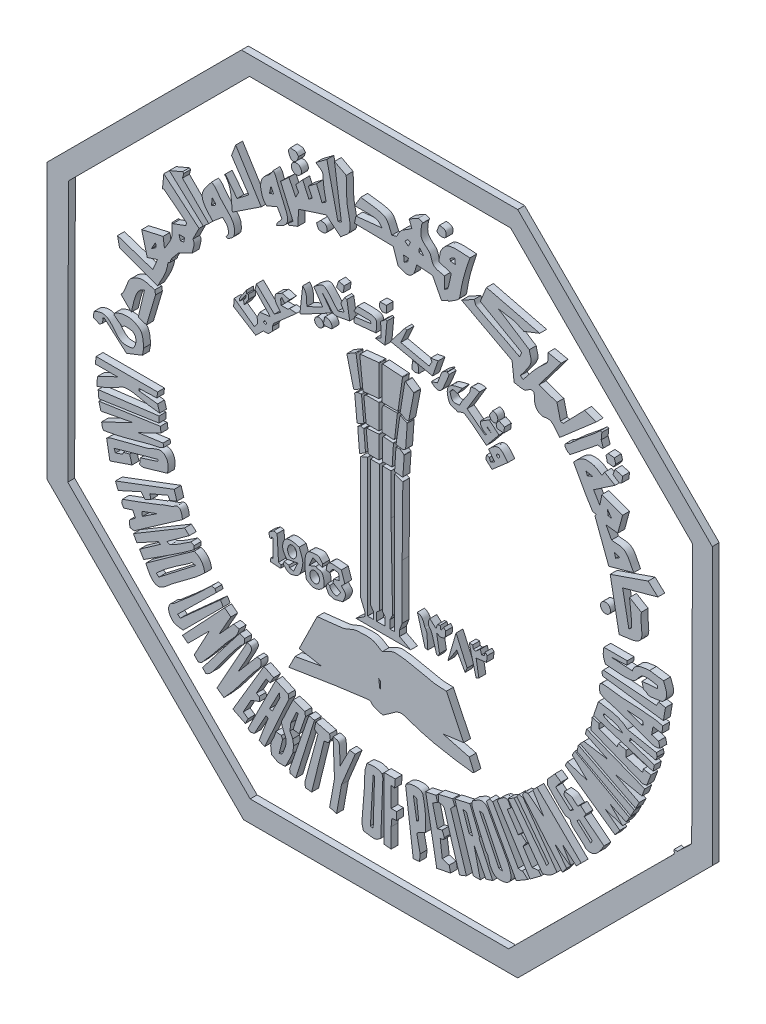
SolidWorks part; units mm, degrees
ref_plane "Front Plane" through (0, 0, 0) normal (0, 0, 1) x (1, 0, 0)
ref_plane "Top Plane" through (0, 0, 0) normal (0, 1, 0) x (1, 0, 0)
ref_plane "Right Plane" through (0, 0, 0) normal (1, 0, 0) x (0, 0, -1)
sketch "Sketch3" plane through (0, 0, 0) normal (0, 0, 1) x (1, 0, 0)
  line L0 (183.5, 512) -> (917.5, 512) construction
  line L1 (600.8403, 692.74) -> (593.4471, 654.6425)
  line L2 (592.7925, 654.1027) -> (589.1017, 654.1027)
  line L3 (588.7776, 654.1868) -> (581.4635, 658.2556)
  line L4 (581.1293, 658.9439) -> (587.8348, 700.7525)
  line L5 (588.8625, 701.202) -> (600.5551, 693.4222)
  line L6 (577.2635, 658.4827) -> (555.6388, 658.4827)
  line L7 (554.972, 659.1494) -> (554.972, 706.3571)
  line L8 (555.6867, 707.0222) -> (583.8131, 704.9983)
  line L9 (584.4252, 704.2383) -> (577.9235, 659.0545)
  line L10 (549.9929, 705.9322) -> (523.2286, 703.097)
  line L11 (522.6358, 702.3637) -> (527.2139, 659.1457)
  line L12 (527.9472, 658.5529) -> (550.1334, 660.9031)
  line L13 (550.7299, 661.5661) -> (550.7299, 705.2691)
  line L14 (516.2122, 701.2896) -> (504.2243, 694.3379)
  line L15 (503.9122, 693.5982) -> (513.7065, 654.7226)
  line L16 (514.6876, 654.3087) -> (523.3973, 659.3593)
  line L17 (523.7213, 660.0414) -> (517.2051, 700.818)
  line L18 (588.6228, 616.3203) -> (585.1923, 614.331)
  line L19 (584.7629, 614.2479) -> (575.7308, 615.5475)
  line L20 (575.1658, 616.3025) -> (580.6493, 654.4101)
  line L21 (581.5764, 654.926) -> (590.8926, 650.853)
  line L22 (591.2907, 650.1954) -> (588.9535, 616.8505)
  line L23 (554.972, 658.4827) -> (554.972, 651.522)
  line L24 (554.972, 651.3934) -> (554.972, 621.5863)
  line L25 (555.6388, 620.9195) -> (559.0252, 620.9195)
  line L26 (559.0252, 620.9195) -> (569.6504, 620.1748)
  line L27 (569.8466, 620.1901) -> (572.5562, 620.8139)
  line L28 (573.0691, 621.3872) -> (576.974, 655.2418)
  line L29 (576.3116, 655.985) -> (557.211, 655.985)
  line L30 (556.592, 655.5662) -> (555.0199, 651.6413)
  line L31 (550.7299, 655.3182) -> (550.7299, 620.8346)
  line L32 (550.0631, 620.1678) -> (532.4115, 620.1678)
  line L33 (531.7479, 620.77) -> (528.5662, 653.4609)
  line L34 (528.8679, 654.0855) -> (531.6413, 655.8782)
  line L35 (532.0032, 655.985) -> (550.0631, 655.985)
  line L36 (525.1693, 653.2014) -> (528.4808, 619.1764)
  line L37 (528.0939, 618.5052) -> (519.538, 614.6026)
  line L38 (518.5977, 615.1446) -> (515.1964, 650.0925)
  line L39 (515.4981, 650.7171) -> (519.3922, 653.2343)
  line L40 (519.6896, 653.338) -> (524.4411, 653.8004)
  line L41 (575.6634, 612.7708) -> (580.838, 612.7708)
  line L42 (581.2309, 612.6428) -> (586.6507, 608.6901)
  line L43 (586.9229, 608.1048) -> (584.9596, 580.0932)
  line L44 (584.218, 579.4774) -> (573.6441, 580.697)
  line L45 (573.055, 581.4015) -> (574.9979, 612.1461)
  line L46 (570.0808, 398.9926) -> (567.8514, 519.8754)
  line L47 (571.3406, 614.6961) -> (569.4688, 585.0752)
  line L48 (568.8033, 584.4505) -> (556.5327, 584.4505)
  line L49 (555.8659, 585.1173) -> (555.8659, 615.743)
  line L50 (556.58, 616.4081) -> (570.7224, 615.4032)
  line L51 (550.7299, 615.7346) -> (550.7299, 584.4371)
  line L52 (550.0631, 583.7703) -> (535.4407, 583.7703)
  line L53 (534.777, 584.3725) -> (531.872, 614.2211)
  line L54 (532.4807, 614.9501) -> (550.0082, 616.3991)
  line L55 (528.5686, 611.7562) -> (530.8774, 583.8285)
  line L56 (530.5749, 583.2136) -> (523.2513, 578.4794)
  line L57 (522.2248, 578.9845) -> (519.6423, 610.2237)
  line L58 (519.9448, 610.8386) -> (523.3827, 613.0609)
  line L59 (523.8705, 613.1558) -> (528.03, 612.3561)
  line L60 (584.9102, 573.7645) -> (584.002, 475.2058)
  line L61 (584.002, 475.2058) -> (584.002, 396.0105)
  line L62 (583.9958, 395.9763) -> (580.1051, 385.6875)
  line L63 (580.0989, 385.6534) -> (580.0989, 377.5979)
  line L64 (580.1498, 377.5128) -> (596.2129, 368.9076)
  line L66 (596.2129, 368.9076) -> (547.0228, 368.9076)
  line L67 (546.9262, 368.8111) -> (546.9262, 369.0041)
  line L68 (546.8297, 368.9076) -> (517.4836, 368.9076)
  line L69 (517.4301, 369.0845) -> (530.4913, 377.7813)
  line L70 (530.5343, 377.8617) -> (530.5343, 382.2535)
  line L71 (530.5269, 382.2908) -> (523.8569, 398.248)
  line L72 (523.8494, 398.2853) -> (523.8494, 574.8342)
  line L73 (523.9087, 574.9233) -> (533.6801, 579.0077)
  line L74 (533.8139, 578.9186) -> (533.8139, 380.138)
  line L75 (533.9104, 380.0414) -> (542.1654, 380.0414)
  line L76 (542.2619, 380.138) -> (542.2619, 390.2402)
  line L77 (542.2457, 390.2937) -> (538.0541, 396.5888)
  line L78 (538.0379, 396.6423) -> (538.0379, 578.967)
  line L79 (538.1344, 579.0636) -> (551.2096, 579.0636)
  line L80 (551.3061, 578.967) -> (551.3061, 476.3053)
  line L82 (551.3061, 476.3053) -> (551.3061, 395.4793)
  line L83 (551.271, 395.4048) -> (547.0491, 391.9257)
  line L84 (547.0139, 391.8512) -> (547.0139, 380.138)
  line L85 (547.1104, 380.0414) -> (559.1217, 380.0414)
  line L86 (559.2182, 380.138) -> (559.2182, 391.8621)
  line L87 (559.1962, 391.9235) -> (555.3537, 396.5864)
  line L88 (555.3317, 396.6478) -> (555.3317, 578.967)
  line L89 (555.4282, 579.0636) -> (567.7548, 579.0636)
  line L90 (567.8514, 578.967) -> (567.8514, 519.8754)
  line L93 (570.0694, 398.9479) -> (566.3034, 391.9181)
  line L94 (566.292, 391.8725) -> (566.292, 380.138)
  line L95 (566.3885, 380.0414) -> (572.9186, 380.0414)
  line L96 (573.0151, 380.138) -> (573.0151, 577.8627)
  line L97 (573.1435, 577.9538) -> (584.8456, 573.8565)
  arc A0 (523.2513, 578.4794) -> (522.2248, 578.9845) centre (522.8893, 579.0394) cw
  arc A1 (530.8774, 583.8285) -> (530.5749, 583.2136) centre (530.2129, 583.7735) cw
  arc A2 (519.6423, 610.2237) -> (519.9448, 610.8386) centre (520.3068, 610.2787) cw
  arc A3 (523.3827, 613.0609) -> (523.8705, 613.1558) centre (523.7446, 612.501) cw
  arc A4 (528.5686, 611.7562) -> (528.03, 612.3561) centre (527.9041, 611.7013) ccw
  arc A5 (531.872, 614.2211) -> (532.4807, 614.9501) centre (532.5357, 614.2856) cw
  arc A6 (550.7299, 615.7346) -> (550.0082, 616.3991) centre (550.0631, 615.7346) ccw
  arc A7 (535.4407, 583.7703) -> (534.777, 584.3725) centre (535.4407, 584.4371) cw
  arc A8 (550.7299, 584.4371) -> (550.0631, 583.7703) centre (550.0631, 584.4371) cw
  arc A9 (556.5327, 584.4505) -> (555.8659, 585.1173) centre (556.5327, 585.1173) cw
  arc A10 (569.4688, 585.0752) -> (568.8033, 584.4505) centre (568.8033, 585.1173) cw
  arc A11 (555.8659, 615.743) -> (556.58, 616.4081) centre (556.5327, 615.743) cw
  arc A12 (571.3406, 614.6961) -> (570.7224, 615.4032) centre (570.6752, 614.7381) ccw
  arc A13 (586.6507, 608.6901) -> (586.9229, 608.1048) centre (586.2578, 608.1514) cw
  arc A14 (580.838, 612.7708) -> (581.2309, 612.6428) centre (580.838, 612.1041) cw
  arc A15 (575.6634, 612.7708) -> (574.9979, 612.1461) centre (575.6634, 612.1041) ccw
  arc A16 (573.6441, 580.697) -> (573.055, 581.4015) centre (573.7205, 581.3594) cw
  arc A17 (584.9596, 580.0932) -> (584.218, 579.4774) centre (584.2944, 580.1398) cw
  arc A18 (515.1964, 650.0925) -> (515.4981, 650.7171) centre (515.86, 650.1571) cw
  arc A19 (519.3922, 653.2343) -> (519.6896, 653.338) centre (519.7542, 652.6744) cw
  arc A20 (525.1693, 653.2014) -> (524.4411, 653.8004) centre (524.5057, 653.1368) ccw
  arc A21 (519.538, 614.6026) -> (518.5977, 615.1446) centre (519.2613, 615.2092) cw
  arc A22 (528.4808, 619.1764) -> (528.0939, 618.5052) centre (527.8172, 619.1118) cw
  arc A23 (532.4115, 620.1678) -> (531.7479, 620.77) centre (532.4115, 620.8346) cw
  arc A24 (528.5662, 653.4609) -> (528.8679, 654.0855) centre (529.2299, 653.5255) cw
  arc A25 (531.6413, 655.8782) -> (532.0032, 655.985) centre (532.0032, 655.3182) cw
  arc A26 (550.7299, 655.3182) -> (550.0631, 655.985) centre (550.0631, 655.3182) ccw
  arc A27 (550.7299, 620.8346) -> (550.0631, 620.1678) centre (550.0631, 620.8346) cw
  arc A28 (554.972, 621.5863) -> (555.6388, 620.9195) centre (555.6388, 621.5863) ccw
  arc A29 (569.6504, 620.1748) -> (569.8466, 620.1901) centre (569.697, 620.8399) ccw
  arc A30 (572.5562, 620.8139) -> (573.0691, 621.3872) centre (572.4067, 621.4636) ccw
  arc A31 (555.0199, 651.6413) -> (554.972, 651.3934) centre (555.6388, 651.3934) ccw
  arc A32 (557.211, 655.985) -> (556.592, 655.5662) centre (557.211, 655.3182) ccw
  arc A33 (576.974, 655.2418) -> (576.3116, 655.985) centre (576.3116, 655.3182) ccw
  arc A34 (588.6228, 616.3203) -> (588.9535, 616.8505) centre (588.2883, 616.8972) ccw
  arc A35 (585.1923, 614.331) -> (584.7629, 614.2479) centre (584.8578, 614.9078) cw
  arc A36 (575.7308, 615.5475) -> (575.1658, 616.3025) centre (575.8258, 616.2075) cw
  arc A37 (580.6493, 654.4101) -> (581.5764, 654.926) centre (581.3093, 654.3151) cw
  arc A38 (591.2907, 650.1954) -> (590.8926, 650.853) centre (590.6255, 650.242) ccw
  arc A39 (513.7065, 654.7226) -> (514.6876, 654.3087) centre (514.3531, 654.8855) ccw
  arc A40 (523.3973, 659.3593) -> (523.7213, 660.0414) centre (523.0629, 659.9362) ccw
  arc A41 (504.2243, 694.3379) -> (503.9122, 693.5982) centre (504.5588, 693.7611) ccw
  arc A42 (516.2122, 701.2896) -> (517.2051, 700.818) centre (516.5467, 700.7128) cw
  arc A43 (527.2139, 659.1457) -> (527.9472, 658.5529) centre (527.877, 659.216) ccw
  arc A44 (550.1334, 660.9031) -> (550.7299, 661.5661) centre (550.0631, 661.5661) ccw
  arc A45 (523.2286, 703.097) -> (522.6358, 702.3637) centre (523.2989, 702.434) ccw
  arc A46 (549.9929, 705.9322) -> (550.7299, 705.2691) centre (550.0631, 705.2691) cw
  arc A47 (555.6388, 658.4827) -> (554.972, 659.1494) centre (555.6388, 659.1494) cw
  arc A48 (577.2635, 658.4827) -> (577.9235, 659.0545) centre (577.2635, 659.1494) ccw
  arc A49 (581.4635, 658.2556) -> (581.1293, 658.9439) centre (581.7877, 658.8383) cw
  arc A50 (589.1017, 654.1027) -> (588.7776, 654.1868) centre (589.1017, 654.7695) cw
  arc A51 (593.4471, 654.6425) -> (592.7925, 654.1027) centre (592.7925, 654.7695) cw
  arc A52 (554.972, 706.3571) -> (555.6867, 707.0222) centre (555.6388, 706.3571) cw
  arc A53 (583.8131, 704.9983) -> (584.4252, 704.2383) centre (583.7652, 704.3332) cw
  arc A54 (587.8348, 700.7525) -> (588.8625, 701.202) centre (588.4931, 700.6469) cw
  arc A55 (600.8403, 692.74) -> (600.5551, 693.4222) centre (600.1857, 692.8671) ccw
  arc A56 (566.3034, 391.9181) -> (566.292, 391.8725) centre (566.3885, 391.8725) ccw
  arc A57 (570.0808, 398.9926) -> (570.0694, 398.9479) centre (569.9843, 398.9935) cw
  arc A58 (572.9186, 380.0414) -> (573.0151, 380.138) centre (572.9186, 380.138) ccw
  arc A59 (566.292, 380.138) -> (566.3885, 380.0414) centre (566.3885, 380.138) ccw
  arc A60 (547.0139, 380.138) -> (547.1104, 380.0414) centre (547.1104, 380.138) ccw
  arc A61 (559.1217, 380.0414) -> (559.2182, 380.138) centre (559.1217, 380.138) ccw
  arc A62 (559.2182, 391.8621) -> (559.1962, 391.9235) centre (559.1217, 391.8621) ccw
  arc A63 (555.3537, 396.5864) -> (555.3317, 396.6478) centre (555.4282, 396.6478) cw
  arc A64 (551.3061, 395.4793) -> (551.271, 395.4048) centre (551.2096, 395.4793) cw
  arc A65 (547.0491, 391.9257) -> (547.0139, 391.8512) centre (547.1104, 391.8512) ccw
  arc A66 (533.8139, 380.138) -> (533.9104, 380.0414) centre (533.9104, 380.138) ccw
  arc A67 (542.1654, 380.0414) -> (542.2619, 380.138) centre (542.1654, 380.138) ccw
  arc A68 (542.2619, 390.2402) -> (542.2457, 390.2937) centre (542.1654, 390.2402) ccw
  arc A69 (538.0541, 396.5888) -> (538.0379, 396.6423) centre (538.1344, 396.6423) cw
  arc A70 (523.8569, 398.248) -> (523.8494, 398.2853) centre (523.9459, 398.2853) cw
  arc A71 (530.5343, 382.2535) -> (530.5269, 382.2908) centre (530.4378, 382.2535) ccw
  arc A72 (530.4913, 377.7813) -> (530.5343, 377.8617) centre (530.4378, 377.8617) ccw
  arc A73 (517.4836, 368.9076) -> (517.4301, 369.0845) centre (517.4836, 369.0041) cw
  arc A74 (546.9262, 369.0041) -> (546.8297, 368.9076) centre (546.8297, 369.0041) cw
  arc A75 (547.0228, 368.9076) -> (546.9262, 368.8111) centre (547.0228, 368.8111) ccw
  arc A78 (580.0989, 377.5979) -> (580.1498, 377.5128) centre (580.1954, 377.5979) ccw
  arc A79 (580.1051, 385.6875) -> (580.0989, 385.6534) centre (580.1954, 385.6534) ccw
  arc A80 (584.002, 396.0105) -> (583.9958, 395.9763) centre (583.9055, 396.0105) cw
  arc A83 (571.0345, 513.711) -> (571.0506, 513.6566) centre (570.9541, 513.6575) cw
  arc A85 (523.8494, 574.8342) -> (523.9087, 574.9233) centre (523.9459, 574.8342) cw
  arc A86 (533.6801, 579.0077) -> (533.8139, 578.9186) centre (533.7174, 578.9186) cw
  arc A87 (538.0379, 578.967) -> (538.1344, 579.0636) centre (538.1344, 578.967) cw
  arc A88 (551.2096, 579.0636) -> (551.3061, 578.967) centre (551.2096, 578.967) cw
  arc A89 (555.3317, 578.967) -> (555.4282, 579.0636) centre (555.4282, 578.967) cw
  arc A90 (567.7548, 579.0636) -> (567.8514, 578.967) centre (567.7548, 578.967) cw
  arc A91 (573.0151, 577.8627) -> (573.1435, 577.9538) centre (573.1116, 577.8627) cw
  arc A92 (584.9102, 573.7645) -> (584.8456, 573.8565) centre (584.8137, 573.7654) ccw
  point P134 (573.0151, 580.7696)
  point P157 (550.7299, 620.1678)
  point P193 (550.7299, 660.9663)
  point P205 (581.0553, 658.4827)
extrude "Boss-Extrude2" add sketch "Sketch3" along normal blind 10 contours L1 A55 L5 A54 L4 A49 L3 A50 L2 A51 | A53 L8 A52 L7 A47 L6 A48 L9 | A46 L10 A45 L11 A43 L12 A44 L13 | A42 L14 A41 L15 A39 L16 A40 L17 | A22 L36 A20 L40 A19 L39 A18 L38 A21 L37 | A27 L31 A26 L35 A25 L34 A24 L33 A23 L32 | L28 A33 L29 A32 L30 A31 L24 A28 L25 L26 A29 L27 A30 | L22 A38 L21 A37 L20 A36 L19 A35 L18 A34 | A17 L43 A13 L42 A14 L41 A15 L45 A16 L44 | L47 A12 L50 A11 L49 A9 L48 A10 | A8 L51 A6 L54 A5 L53 A7 L52 | L55 A4 L59 A3 L58 A2 L57 A0 L56 A1 | L96 L0 L60 A92 L97 A91 | L88 L0 A83 L90 A90 L89 A89 | L78 L0 L80 A88 L79 A87 | L72 L0 L74 A86 L73 A85 | L0 L72 A70 L71 A71 L70 A72 L69 A73 L68 A74 L67 A75 L66 L64 A78 L63 A79 L62 A80 L61 L60 L96 A58 L95 A59 L94 A56 L93 A57 L88 A63 L87 A62 L86 A61 L85 A60 L84 A65 L83 A64 L82 region at (528.8848, 544.5013, 0) region at (528.8316, 510.3655, 0) region at (544.672, 545.5316, 0) region at (561.5958, 545.5106, 0) region at (578.7603, 544.2386, 0) region at (590.7504, 676.9045, 0) region at (568.0657, 683.279, 0) region at (537.7914, 682.8034, 0) region at (514.4326, 678.3345, 0) region at (583.7669, 633.3176, 0) region at (565.1082, 638.8163, 0) region at (540.4252, 638.4974, 0) region at (521.8097, 634.6428, 0) region at (579.9264, 595.9612, 0) region at (563.1079, 600.5377, 0) region at (542.0674, 600.1985, 0) region at (525.2118, 596.484, 0)
sketch "Sketch4" plane through (0, 0, 0) normal (0, 0, 1) x (1, 0, 0)
  line L0 (183.5, 512) -> (917.5, 512) construction
  line L1 (648, 343) -> (673, 291)
  line L2 (673, 291) -> (643, 287)
  line L3 (643, 287) -> (681, 277)
  line L4 (681, 277) -> (688, 261)
  line L5 (420, 259) -> (429, 277)
  line L6 (429, 277) -> (467, 284)
  line L7 (467, 284) -> (435, 290)
  line L8 (435, 290) -> (461, 343)
  line L9 (550, 310) -> (553, 307)
  line L10 (553, 307) -> (552, 295)
  line L11 (552, 295) -> (550, 310)
  line L12 (681, 420) -> (686, 420)
  line L13 (686, 420) -> (687, 415)
  line L14 (687, 415) -> (690, 414)
  line L15 (690, 414) -> (697, 420)
  line L16 (697, 420) -> (699, 414)
  line L17 (699, 414) -> (703, 415)
  line L18 (703, 415) -> (704, 420)
  line L19 (704, 420) -> (707, 417)
  line L20 (707, 417) -> (706, 408)
  line L21 (706, 408) -> (691, 406)
  line L22 (691, 406) -> (695, 383)
  line L23 (695, 383) -> (691, 381)
  line L24 (691, 381) -> (681, 420)
  line L25 (662, 423) -> (678, 387)
  line L26 (678, 387) -> (675, 380)
  line L27 (675, 380) -> (663, 402)
  line L28 (663, 402) -> (650, 382)
  line L29 (650, 382) -> (662, 423)
  line L30 (624, 422) -> (633, 414)
  line L31 (633, 414) -> (635, 420)
  line L32 (635, 420) -> (639, 421)
  line L33 (639, 421) -> (640, 415)
  line L34 (640, 415) -> (644, 421)
  line L35 (644, 421) -> (647, 418)
  line L36 (635, 409) -> (634, 408)
  line L37 (634, 408) -> (638, 385)
  line L38 (638, 385) -> (636, 381)
  line L39 (621, 381) -> (617, 382)
  line L40 (617, 382) -> (606, 421)
  line L41 (496, 419) -> (501, 404)
  line L42 (501, 404) -> (496, 399)
  line L43 (498, 380) -> (486, 377)
  line L44 (486, 377) -> (478, 379)
  line L45 (476, 392) -> (479, 391)
  line L46 (490, 383) -> (495, 390)
  line L47 (495, 390) -> (484, 397)
  line L48 (484, 397) -> (485, 402)
  line L49 (485, 402) -> (493, 404)
  line L50 (493, 404) -> (492, 413)
  line L51 (479, 407) -> (474, 408)
  line L52 (469, 413) -> (468, 408)
  line L53 (468, 408) -> (455, 414)
  line L54 (455, 414) -> (449, 401)
  line L55 (449, 401) -> (459, 405)
  line L56 (412, 384) -> (413, 388)
  line L57 (413, 388) -> (420, 387)
  line L58 (420, 387) -> (421, 384)
  line L59 (421, 384) -> (427, 383)
  line L60 (427, 383) -> (433, 396)
  line L61 (433, 396) -> (417, 393)
  line L62 (398, 419) -> (403, 418)
  line L63 (403, 418) -> (405, 383)
  line L64 (405, 383) -> (409, 382)
  line L65 (409, 382) -> (408, 377)
  line L66 (408, 377) -> (393, 378)
  line L67 (393, 378) -> (394, 383)
  line L68 (394, 383) -> (397, 384)
  line L69 (397, 384) -> (397, 409)
  line L70 (397, 409) -> (395, 410)
  line L71 (395, 410) -> (394, 407)
  line L72 (394, 407) -> (392, 408)
  line L73 (392, 408) -> (391, 414)
  line L74 (391, 414) -> (398, 419)
  arc A0 (490, 383) -> (479, 391) centre (488.9641, 393.1381) cw
  ellipse E0 centre (457.3409, 390.9087) end of major axis (457.2391, 382.8787) minor radius 7.002
  ellipse E1 centre (424.7461, 406.1429) end of major axis (423.9625, 397.8033) minor radius 6.5743
  spline S0 degree 3 poles (461, 343) (473, 344.3333) (485.0293, 345.4249) (497, 347) (504.6298, 348.0039) (511.3194, 353.52) (519, 354) (542.4461, 355.4654) (541.6131, 354.3668) (555, 346) knots 0 0 0 0 1 1 1 2 2 2 3 3 3 3
  spline S1 degree 3 poles (555, 346) (561.6667, 348.6667) (567.8223, 354.1889) (575, 354) (593.9554, 353.5012) (612.2497, 346.8254) (631, 344) (636.6131, 343.1542) (642.3333, 343.3333) (648, 343) knots 0 0 0 0 1 1 1 2 2 2 3 3 3 3
  spline S2 degree 3 poles (688, 261) (687.3333, 260.6667) (686.7404, 259.9143) (686, 260) (560.9858, 274.4645) (599.5056, 298.6405) (556, 267) knots 0 0 0 0 1 1 1 2 2 2 2
  spline S3 degree 3 poles (556, 267) (551.6667, 268.3333) (547.1345, 269.1395) (543, 271) (540.3851, 272.1767) (538.8539, 276.2784) (536, 276) (497.105, 272.2054) (458.6667, 264.6667) (420, 259) knots 0 0 0 0 1 1 1 2 2 2 3 3 3 3
  spline S4 degree 3 poles (647, 418) (646.4925, 413.9401) (647.7163, 408.1433) (642, 407) (637.5104, 406.1021) (636.9744, 407.0256) (635, 409) knots 0 0 0 0 1 1 1 2 2 2 2
  spline S5 degree 3 poles (636, 381) (635.3333, 381.3333) (634.3084, 381.3215) (634, 382) (632.5599, 385.1682) (632.0133, 388.6707) (631, 392) (629.6799, 396.3374) (628.5249, 400.7303) (627, 405) (625.2405, 409.9267) (621.4375, 410.8122) (622, 417) (622.1625, 418.7877) (623.3333, 420.3333) (624, 422) knots 0 0 0 0 1 1 1 2 2 2 3 3 3 4 4 4 5 5 5 5
  spline S6 degree 3 poles (606, 421) (613.9669, 419.0083) (614.422, 413.8748) (617, 407) (617.1655, 406.5586) (617.8143, 406.4333) (618, 406) (618.8305, 404.0623) (619.7488, 402.0932) (620, 400) (620.7556, 393.7031) (620.6667, 387.3333) (621, 381) knots 0 0 0 0 1 1 1 2 2 2 3 3 3 4 4 4 4
  spline S7 degree 3 poles (474, 408) (474.6184, 412.3287) (475.4033, 420) (482, 420) (486.6786, 420) (491.3333, 419.3333) (496, 419) knots 0 0 0 0 1 1 1 2 2 2 2
  spline S8 degree 3 poles (496, 399) (498.2524, 396.1845) (502.5099, 393.5693) (502, 390) (501.4923, 386.446) (499.3333, 383.3333) (498, 380) knots 0 0 0 0 1 1 1 2 2 2 2
  spline S9 degree 3 poles (478, 379) (473.1972, 388.6055) (472.8927, 384.2318) (476, 392) knots 0 0 0 0 1 1 1 1
  spline S10 degree 3 poles (492, 413) (483.6074, 414.3988) (482.9153, 414.8306) (479, 407) knots 0 0 0 0 1 1 1 1
  spline S11 degree 3 poles (459, 405) (462.9497, 401.0503) (466.291, 405.5015) (469, 399) (470.4312, 395.5651) (472.3667, 387.8458) (470, 384) (466.2114, 377.8435) (456.0336, 374.1732) (450, 379) (448.3333, 380.3333) (445.4186, 380.9071) (445, 383) (443.8884, 388.5581) (439.3004, 417.1527) (451, 419) (464.5018, 421.1319) (463.2758, 420.1552) (469, 413) knots 0 0 0 0 1 1 1 2 2 2 3 3 3 4 4 4 5 5 5 6 6 6 6
  spline S12 degree 3 poles (417, 393) (413.8841, 397.1545) (410.598, 401.3723) (411, 407) (412.0845, 422.1827) (424.2965, 420.5678) (435, 417) knots 0 0 0 0 1 1 1 2 2 2 2
  spline S13 degree 3 poles (435, 417) (436.926, 410.7406) (440.9715, 404.4765) (440, 398) (439.1458, 392.3055) (437.3284, 381.6173) (430, 379) (419.4852, 375.2447) (418.5751, 377.4249) (412, 384) knots 0 0 0 0 1 1 1 2 2 2 3 3 3 3
extrude "Boss-Extrude3" add sketch "Sketch4" along normal blind 10 separate body
sketch "Sketch6" plane through (0, 0, 0) normal (0, 0, 1) x (1, 0, 0)
  line L0 (183.5, 512) -> (917.5, 512) construction
  line L1 (940, 627) -> (954, 614)
  line L2 (954, 614) -> (903, 600)
  line L3 (903, 600) -> (912, 553)
  line L4 (913, 593) -> (930, 583)
  line L5 (898, 539) -> (885, 608)
  line L6 (885, 608) -> (940, 627)
  line L7 (873, 726) -> (877, 732)
  line L8 (877, 732) -> (892, 723)
  line L9 (892, 723) -> (861, 702)
  line L10 (861, 702) -> (870, 687)
  line L11 (870, 687) -> (873, 702)
  line L12 (873, 702) -> (903, 691)
  line L13 (903, 691) -> (896, 665)
  line L14 (896, 665) -> (879, 667)
  line L15 (879, 667) -> (887, 652)
  line L16 (919, 627) -> (883, 617)
  line L17 (883, 617) -> (863, 670)
  line L18 (863, 670) -> (865, 673)
  line L19 (850, 720) -> (860, 718)
  line L20 (860, 718) -> (852, 715)
  line L21 (852, 715) -> (850, 720)
  line L22 (881, 688) -> (887, 679)
  line L23 (887, 679) -> (882, 680)
  line L24 (882, 680) -> (881, 688)
  line L25 (891, 639) -> (899, 636)
  line L26 (899, 636) -> (893, 632)
  line L27 (893, 632) -> (891, 639)
  line L28 (892, 743) -> (903, 740)
  line L29 (903, 740) -> (902, 731)
  line L30 (902, 731) -> (898, 729)
  line L31 (898, 729) -> (889, 735)
  line L32 (889, 735) -> (892, 743)
  line L33 (882, 758) -> (891, 757)
  line L34 (891, 757) -> (893, 750)
  line L35 (893, 750) -> (890, 745)
  line L36 (890, 745) -> (881, 746)
  line L37 (881, 746) -> (879, 754)
  line L38 (879, 754) -> (882, 758)
  line L39 (871, 781) -> (873, 780)
  line L40 (873, 780) -> (872, 770)
  line L41 (872, 770) -> (875, 761)
  line L42 (875, 761) -> (874, 760)
  line L43 (874, 760) -> (867, 761)
  line L44 (867, 761) -> (827, 729)
  line L45 (706, 878) -> (783, 859)
  line L46 (783, 859) -> (760, 850)
  line L47 (723, 860) -> (768, 831)
  line L48 (755, 792) -> (759, 789)
  line L49 (795, 841) -> (814, 837)
  line L50 (814, 837) -> (782, 794)
  line L51 (782, 794) -> (808, 785)
  line L52 (808, 785) -> (813, 764)
  line L53 (813, 764) -> (817, 763)
  line L54 (817, 763) -> (848, 795)
  line L55 (848, 795) -> (865, 789)
  line L56 (865, 789) -> (812, 743)
  line L57 (746, 779) -> (743, 805)
  line L58 (743, 805) -> (670, 844)
  line L59 (670, 844) -> (688, 854)
  line L60 (754, 815) -> (757, 822)
  line L61 (757, 822) -> (697, 856)
  line L62 (697, 856) -> (706, 878)
  line L63 (634, 913) -> (638, 922)
  line L64 (645, 862) -> (645, 845)
  line L65 (655, 870) -> (637, 876)
  line L66 (651, 833) -> (650, 834)
  line L67 (650, 834) -> (641, 829)
  line L68 (641, 829) -> (628, 854)
  line L69 (628, 854) -> (605, 856)
  line L70 (578, 841) -> (571, 862)
  line L71 (571, 862) -> (515, 863)
  line L72 (515, 863) -> (517, 873)
  line L73 (517, 873) -> (555, 877)
  line L74 (515, 885) -> (524, 900)
  line L75 (569, 875) -> (576, 877)
  line L76 (598, 898) -> (594, 908)
  line L77 (660, 892) -> (661, 884)
  line L78 (661, 884) -> (654, 885)
  line L79 (654, 885) -> (653, 888)
  line L80 (653, 888) -> (660, 892)
  line L81 (592, 881) -> (596, 880)
  line L82 (596, 880) -> (593, 873)
  line L83 (593, 873) -> (588, 877)
  line L84 (588, 877) -> (592, 881)
  line L85 (609, 880) -> (615, 872)
  line L86 (615, 872) -> (608, 873)
  line L87 (608, 873) -> (609, 880)
  line L88 (586, 859) -> (593, 858)
  line L89 (593, 858) -> (592, 853)
  line L90 (592, 853) -> (587, 850)
  line L91 (587, 850) -> (586, 859)
  line L92 (486, 926) -> (503, 917)
  line L93 (495, 836) -> (474, 853)
  line L94 (474, 853) -> (434, 840)
  line L95 (434, 840) -> (433, 818)
  line L96 (433, 818) -> (420, 813)
  line L97 (420, 813) -> (419, 815)
  line L98 (419, 815) -> (426, 821)
  line L99 (426, 821) -> (408, 862)
  line L100 (408, 862) -> (420, 873)
  line L101 (420, 873) -> (430, 853)
  line L102 (430, 853) -> (434, 861)
  line L103 (434, 861) -> (430, 869)
  line L104 (430, 869) -> (440, 880)
  line L105 (440, 880) -> (449, 860)
  line L106 (449, 860) -> (454, 864)
  line L107 (454, 864) -> (448, 876)
  line L108 (448, 876) -> (460, 885)
  line L109 (460, 885) -> (468, 865)
  line L110 (468, 865) -> (474, 869)
  line L111 (459, 911) -> (475, 923)
  line L112 (475, 923) -> (491, 853)
  line L113 (491, 853) -> (496, 855)
  line L114 (496, 855) -> (486, 926)
  line L115 (463, 829) -> (460, 836)
  line L116 (460, 836) -> (466, 842)
  line L117 (419, 907) -> (422, 911)
  line L118 (402, 804) -> (403, 807)
  line L119 (403, 807) -> (410, 816)
  line L120 (410, 816) -> (403, 828)
  line L121 (403, 828) -> (388, 821)
  line L122 (394, 849) -> (398, 841)
  line L123 (398, 841) -> (392, 839)
  line L124 (392, 839) -> (394, 849)
  line L125 (343, 875) -> (380, 816)
  line L126 (380, 816) -> (339, 789)
  line L127 (327, 830) -> (328, 831)
  line L128 (328, 831) -> (345, 809)
  line L129 (345, 809) -> (362, 822)
  line L130 (362, 822) -> (337, 859)
  line L131 (337, 859) -> (343, 875)
  line L132 (332, 752) -> (329, 753)
  line L133 (329, 753) -> (333, 759)
  line L134 (324, 775) -> (310, 763)
  line L135 (309, 792) -> (314, 787)
  line L136 (314, 787) -> (313, 784)
  line L137 (313, 784) -> (308, 782)
  line L138 (308, 782) -> (309, 792)
  line L139 (266, 803) -> (268, 802)
  line L140 (268, 802) -> (266, 795)
  line L141 (266, 795) -> (304, 757)
  line L142 (304, 757) -> (296, 750)
  line L143 (296, 750) -> (247, 795)
  line L144 (247, 795) -> (266, 803)
  line L145 (239, 787) -> (290, 744)
  line L146 (290, 744) -> (281, 726)
  line L147 (230, 642) -> (175, 662)
  line L148 (175, 662) -> (172, 676)
  line L149 (172, 676) -> (223, 659)
  line L150 (223, 659) -> (230, 675)
  line L151 (230, 675) -> (215, 670)
  line L152 (215, 670) -> (207, 701)
  line L153 (207, 701) -> (238, 708)
  line L154 (238, 708) -> (240, 694)
  line L155 (251, 732) -> (252, 731)
  line L156 (252, 731) -> (271, 738)
  line L157 (271, 738) -> (272, 742)
  line L158 (272, 742) -> (239, 768)
  line L159 (239, 768) -> (237, 767)
  line L160 (237, 767) -> (239, 787)
  line L161 (261, 722) -> (269, 722)
  line L162 (269, 722) -> (268, 716)
  line L163 (268, 716) -> (263, 715)
  line L164 (263, 715) -> (261, 722)
  line L165 (227, 695) -> (228, 689)
  line L166 (228, 689) -> (221, 684)
  line L167 (221, 684) -> (227, 695)
  line L168 (226, 635) -> (227, 629)
  line L169 (227, 629) -> (214, 585)
  line L170 (214, 585) -> (202, 589)
  line L171 (202, 589) -> (211, 627)
  line L172 (192, 590) -> (177, 605)
  line L173 (210, 554) -> (208, 544)
  line L174 (208, 544) -> (185, 535)
  line L175 (185, 535) -> (153, 563)
  line L176 (153, 563) -> (150, 562)
  line L177 (150, 562) -> (151, 561)
  line L178 (146, 552) -> (137, 556)
  line L179 (137, 556) -> (138, 564)
  line L180 (182, 568) -> (179, 565)
  line L181 (179, 565) -> (167, 574)
  circle A0 centre (878.2736, 562.4651) radius 7.2457
  arc A1 (647, 911) -> (634, 913) centre (641.3692, 917.65) cw
  circle A2 centre (430.8825, 889.0468) radius 7.3261
  spline S0 degree 3 poles (912, 553) (913.3333, 554.3333) (915.8366, 555.1215) (916, 557) (916.6967, 565.0123) (913.5914, 584.1283) (913, 593) knots 0 0 0 0 1 1 1 2 2 2 2
  spline S1 degree 3 poles (930, 583) (929.6465, 577.3444) (929.6672, 571.6569) (930, 566) (930.3132, 560.6759) (931.7521, 555.0373) (930, 550) (927.8203, 543.7334) (919.3178, 541.8863) (914, 541) (908.6983, 540.1164) (903.3333, 539.6667) (898, 539) knots 0 0 0 0 1 1 1 2 2 2 3 3 3 4 4 4 4
  spline S2 degree 3 poles (832, 722) (834.3333, 724.3333) (836.2544, 727.1696) (839, 729) (842.3512, 731.2342) (845.9749, 733.8562) (850, 734) (861.8777, 734.4242) (865.2374, 731.175) (873, 726) knots 0 0 0 0 1 1 1 2 2 2 3 3 3 3
  spline S3 degree 3 poles (887, 652) (893.3333, 650.6667) (900.8998, 651.9845) (906, 648) (912.4876, 642.9316) (914.6667, 634) (919, 627) knots 0 0 0 0 1 1 1 2 2 2 2
  spline S4 degree 3 poles (865, 673) (863, 673.6667) (860.1776, 673.2514) (859, 675) (848.9073, 689.9861) (841, 706.3333) (832, 722) knots 0 0 0 0 1 1 1 2 2 2 2
  spline S5 degree 3 poles (827, 729) (823.1383, 730.2872) (816.9181, 735.9181) (821, 740) (822.0541, 741.0541) (823.787, 741.1335) (825, 742) (830.564, 745.9743) (835.7289, 751.6074) (841, 756) (850.9279, 764.2732) (861.8627, 771.8627) (871, 781) knots 0 0 0 0 1 1 1 2 2 2 3 3 3 4 4 4 4
  spline S6 degree 3 poles (760, 850) (755.3333, 852) (750.9013, 854.6753) (746, 856) (738.4878, 858.0303) (730.6667, 858.6667) (723, 860) knots 0 0 0 0 1 1 1 2 2 2 2
  spline S7 degree 3 poles (768, 831) (768.6667, 825.6667) (771.6997, 820.099) (770, 815) (767.1056, 806.3167) (760, 799.6667) (755, 792) knots 0 0 0 0 1 1 1 2 2 2 2
  spline S8 degree 3 poles (759, 789) (795.8, 838.0667) (795, 817) (795, 841) knots 0 0 0 0 1 1 1 1
  spline S9 degree 3 poles (812, 743) (807.6667, 747.6667) (804.6136, 753.9927) (799, 757) (794.5828, 759.3663) (788.5207, 755.8379) (784, 758) (773.9454, 762.8087) (775.655, 772.4845) (775, 781) knots 0 0 0 0 1 1 1 2 2 2 3 3 3 3
  spline S10 degree 3 poles (775, 781) (773.3333, 781.3333) (771.6343, 782.4669) (770, 782) (766.7002, 781.0572) (764.4054, 777.4257) (761, 777) (755.9947, 776.3743) (751, 778.3333) (746, 779) knots 0 0 0 0 1 1 1 2 2 2 3 3 3 3
  spline S11 degree 3 poles (688, 854) (689.3333, 851.6667) (689.6887, 848.3711) (692, 847) (712.0023, 835.1342) (733.8073, 826.5387) (754, 815) knots 0 0 0 0 1 1 1 2 2 2 2
  spline S12 degree 3 poles (638, 922) (646.8417, 920.7369) (648.4908, 919.9447) (647, 911) knots 0 0 0 0 1 1 1 1
  spline S13 degree 3 poles (594, 908) (610.6266, 915.7591) (603.877, 917.0492) (614, 913) knots 0 0 0 0 1 1 1 1
  spline S14 degree 3 poles (614, 913) (613.3333, 911.6667) (612.1483, 910.4833) (612, 909) (611.4693, 903.6931) (609.9608, 897.9281) (612, 893) (614.2548, 887.5508) (620.6432, 884.8487) (624, 880) (626.7166, 876.076) (626.3764, 870.106) (630, 867) (634.0016, 863.57) (640, 863.6667) (645, 862) knots 0 0 0 0 1 1 1 2 2 2 3 3 3 4 4 4 5 5 5 5
  spline S15 degree 3 poles (645, 845) (646.6667, 846.3333) (649.2073, 847.0183) (650, 849) (652.6724, 855.681) (653.3333, 863) (655, 870) knots 0 0 0 0 1 1 1 2 2 2 2
  spline S16 degree 3 poles (637, 876) (638.3333, 881.6667) (638.0322, 887.9919) (641, 893) (643.6545, 897.4794) (647.9415, 901.7662) (653, 903) (662.3914, 905.2906) (672.3333, 903) (682, 903) knots 0 0 0 0 1 1 1 2 2 2 3 3 3 3
  spline S17 degree 3 poles (682, 903) (657.951, 835.0355) (678.4896, 850.181) (651, 833) knots 0 0 0 0 1 1 1 1
  spline S18 degree 3 poles (605, 856) (603.3333, 851.3333) (603.0706, 845.8894) (600, 842) (592.8275, 832.9148) (586.0699, 838.31) (578, 841) knots 0 0 0 0 1 1 1 2 2 2 2
  spline S19 degree 3 poles (555, 877) (552.3333, 879.3333) (550.4746, 883.3051) (547, 884) (536.5354, 886.0929) (525.6667, 884.6667) (515, 885) knots 0 0 0 0 1 1 1 2 2 2 2
  spline S20 degree 3 poles (524, 900) (535, 898) (546.6722, 898.2822) (557, 894) (563.9195, 891.1309) (565.65, 881.6999) (569, 875) knots 0 0 0 0 1 1 1 2 2 2 2
  spline S21 degree 3 poles (576, 877) (582.5547, 891.748) (586.2611, 888.6089) (598, 898) knots 0 0 0 0 1 1 1 1
  spline S22 degree 3 poles (503, 917) (503.3333, 906.3333) (503.3733, 895.6535) (504, 885) (504.6895, 873.2777) (510.4437, 861.4855) (508, 850) (506.6747, 843.7711) (499.3333, 840.6667) (495, 836) knots 0 0 0 0 1 1 1 2 2 2 3 3 3 3
  spline S23 degree 3 poles (474, 869) (464.446, 909.339) (475.8309, 899.7794) (459, 911) knots 0 0 0 0 1 1 1 1
  spline S24 degree 3 poles (466, 842) (469.7525, 841.3746) (473.9822, 842.0889) (475, 837) (476.8771, 827.6144) (468.7692, 828.1758) (463, 829) knots 0 0 0 0 1 1 1 2 2 2 2
  spline S25 degree 3 poles (422, 911) (432.6565, 909.8159) (429.1889, 912.4148) (434, 906) knots 0 0 0 0 1 1 1 1
  spline S26 degree 3 poles (434, 906) (433, 903.6667) (432.7951, 900.7951) (431, 899) (423.0889, 891.0889) (420.1333, 902.4666) (419, 907) knots 0 0 0 0 1 1 1 2 2 2 2
  spline S27 degree 3 poles (397, 870) (401.3046, 867.8477) (403.5125, 856.4776) (406, 852) (407.2328, 849.7809) (408, 847.3333) (409, 845) (417.6947, 824.7123) (426.921, 812.307) (402, 804) knots 0 0 0 0 1 1 1 2 2 2 3 3 3 3
  spline S28 degree 3 poles (388, 821) (382.9195, 826.0805) (381.5984, 828.5407) (380, 836) (379.5752, 837.9826) (378.8735, 839.9764) (379, 842) (380.1568, 860.5087) (391.8297, 857.0742) (397, 870) knots 0 0 0 0 1 1 1 2 2 2 3 3 3 3
  spline S29 degree 3 poles (339, 789) (338.6667, 789.3333) (338.0469, 789.5309) (338, 790) (336.697, 803.0297) (337.4259, 819.5741) (327, 830) knots 0 0 0 0 1 1 1 2 2 2 2
  spline S30 degree 3 poles (308, 811) (313.496, 809.168) (318.1211, 800.5841) (322, 796) (327.5756, 789.4106) (340.4371, 779.5686) (341, 770) (341.2162, 766.3246) (341.6465, 762.2931) (340, 759) (338.4154, 755.8307) (334.6667, 754.3333) (332, 752) knots 0 0 0 0 1 1 1 2 2 2 3 3 3 4 4 4 4
  spline S31 degree 3 poles (333, 759) (331.7892, 768.6863) (330.6593, 768.3407) (324, 775) knots 0 0 0 0 1 1 1 1
  spline S32 degree 3 poles (310, 763) (288.3448, 784.6552) (291.0114, 790.6137) (308, 811) knots 0 0 0 0 1 1 1 1
  spline S33 degree 3 poles (281, 726) (281.6667, 724.6667) (283.0827, 723.4884) (283, 722) (282.7353, 717.2347) (281, 712.6667) (280, 708) knots 0 0 0 0 1 1 1 2 2 2 2
  spline S34 degree 3 poles (280, 708) (275.3333, 705.6667) (270.6667, 703.3333) (266, 701) (264, 700) (261.5002, 699.6581) (260, 698) (240.3622, 676.295) (254.2444, 683.6222) (245, 679) knots 0 0 0 0 1 1 1 2 2 2 3 3 3 3
  spline S35 degree 3 poles (245, 679) (243.5915, 664.9146) (236.7822, 654.2079) (230, 642) knots 0 0 0 0 1 1 1 1
  spline S36 degree 3 poles (240, 694) (243.3333, 700) (248.0915, 705.4069) (250, 712) (251.856, 718.4118) (250.6667, 725.3333) (251, 732) knots 0 0 0 0 1 1 1 2 2 2 2
  spline S37 degree 3 poles (177, 605) (185.6417, 613.6417) (185.008, 627.9142) (193, 633) (206.7622, 641.7578) (211.6483, 639.1005) (226, 635) knots 0 0 0 0 1 1 1 2 2 2 2
  spline S38 degree 3 poles (211, 627) (196.974, 624.1948) (195.1989, 600.8764) (192, 590) knots 0 0 0 0 1 1 1 1
  spline S39 degree 3 poles (167, 574) (168.3587, 578.076) (167.2166, 577.0069) (172, 579) (183.2527, 583.6886) (196.1099, 582.8901) (205, 574) (209.2402, 569.7598) (209.5048, 558.9517) (210, 554) knots 0 0 0 0 1 1 1 2 2 2 3 3 3 3
  spline S40 degree 3 poles (151, 561) (149.726, 553.356) (151.6221, 556.2166) (146, 552) knots 0 0 0 0 1 1 1 1
  spline S41 degree 3 poles (138, 564) (146.3866, 568.1933) (153.7252, 569.8919) (161, 563) (167.693, 556.6593) (172.7984, 545.5751) (182, 545) (186.006, 544.7496) (190.1921, 544.7307) (194, 546) (195.5811, 546.527) (196.2546, 548.5093) (197, 550) (199.4767, 554.9534) (200.0964, 564.6345) (193, 567) (189.5072, 568.1643) (185.6667, 567.6667) (182, 568) knots 0 0 0 0 1 1 1 2 2 2 3 3 3 4 4 4 5 5 5 6 6 6 6
extrude "Boss-Extrude4" add sketch "Sketch6" along normal blind 10 separate body
sketch "Sketch7" plane through (0, 0, 0) normal (0, 0, 1) x (1, 0, 0)
  line L0 (183.5, 512) -> (917.5, 512) construction
  line L1 (141, 509) -> (230, 509)
  line L2 (230, 509) -> (229, 501)
  line L3 (229, 501) -> (203, 500)
  line L4 (142, 472) -> (143, 485)
  line L5 (143, 485) -> (172, 499)
  line L6 (172, 499) -> (140, 499)
  line L7 (140, 499) -> (141, 509)
  line L8 (234, 468) -> (145, 455)
  line L9 (232.1021, 480) -> (232, 471)
  line L10 (232, 471) -> (145, 458)
  line L11 (145, 458) -> (144, 469)
  line L12 (144, 469) -> (232.1021, 480)
  line L13 (489, 110) -> (496.1795, 150)
  line L14 (234, 468) -> (235, 460)
  line L15 (235, 460) -> (202, 444)
  line L16 (202, 444) -> (238, 449)
  line L17 (238, 449) -> (239, 444)
  line L18 (149, 431) -> (195, 453)
  line L19 (195, 453) -> (148, 444)
  line L20 (148, 444) -> (145, 455)
  line L21 (244.3387, 414.143) -> (209, 404)
  line L22 (209, 404) -> (204, 405)
  line L23 (204, 405) -> (205, 414)
  line L24 (205, 414) -> (230, 422)
  line L25 (230, 422) -> (231, 425)
  line L26 (231, 425) -> (167, 407)
  line L27 (167, 407) -> (169, 402)
  line L28 (169, 402) -> (180, 406)
  line L29 (180, 406) -> (180.5465, 408.7324)
  line L30 (180.5465, 408.7324) -> (189.5745, 410.9894)
  line L31 (189.5745, 410.9894) -> (193, 399)
  line L32 (193, 399) -> (161, 388)
  line L33 (161, 388) -> (156.3387, 414.143)
  line L34 (169, 367) -> (254, 399)
  line L35 (254, 399) -> (258, 386)
  line L36 (258, 386) -> (248, 382)
  line L37 (248, 382) -> (245, 387)
  line L38 (245, 387) -> (219, 376)
  line L39 (219, 376) -> (220, 369)
  line L40 (220, 369) -> (212, 365)
  line L41 (212, 365) -> (206, 372)
  line L42 (206, 372) -> (173, 357)
  line L43 (173, 357) -> (169, 367)
  line L44 (266, 367) -> (196, 318)
  line L45 (196, 318) -> (190, 319)
  line L46 (190, 319) -> (189, 328)
  line L47 (189, 328) -> (198, 335)
  line L48 (198, 335) -> (194, 343)
  line L49 (194, 343) -> (181, 339)
  line L50 (181, 339) -> (178, 344)
  line L51 (178, 344) -> (179, 349)
  line L52 (207, 348) -> (229, 356)
  line L53 (229, 356) -> (208, 342)
  line L54 (208, 342) -> (207, 348)
  line L55 (269, 358) -> (276, 352)
  line L56 (276, 352) -> (243, 328)
  line L57 (278, 345) -> (283, 343)
  line L58 (210, 289) -> (204, 299)
  line L59 (204, 299) -> (234, 320)
  line L60 (234, 320) -> (231, 322)
  line L61 (231, 322) -> (200, 305)
  line L62 (200, 305) -> (195, 314)
  line L63 (195, 314) -> (269, 358)
  line L64 (213, 286) -> (283, 336)
  line L65 (285, 319) -> (232, 278)
  line L66 (232, 278) -> (228, 281)
  line L67 (308, 305) -> (313, 304)
  line L68 (313, 304) -> (315, 300)
  line L69 (315, 300) -> (259, 245)
  line L70 (259, 245) -> (263, 242)
  line L71 (263, 242) -> (321, 294)
  line L72 (321, 294) -> (325, 287)
  line L73 (325, 287) -> (267, 229)
  line L74 (327, 287) -> (336, 280)
  line L75 (336, 280) -> (319, 250)
  line L76 (319, 250) -> (340, 273)
  line L77 (340, 273) -> (348, 271)
  line L78 (289, 200) -> (283, 206)
  line L79 (283, 206) -> (305, 247)
  line L80 (305, 247) -> (274, 216)
  line L81 (274, 216) -> (266, 222)
  line L82 (266, 222) -> (327, 287)
  line L83 (349, 266) -> (356, 263)
  line L84 (300, 191) -> (295, 196)
  line L85 (295, 196) -> (349, 266)
  line L86 (346, 216) -> (374, 249)
  line L87 (374, 249) -> (379, 248)
  line L88 (326, 174) -> (316, 181)
  line L89 (316, 181) -> (360, 260)
  line L90 (384, 242) -> (398, 235)
  line L91 (398, 235) -> (393, 226)
  line L92 (393, 226) -> (387, 228)
  line L93 (387, 228) -> (373, 203)
  line L94 (373, 203) -> (377, 201)
  line L95 (377, 201) -> (378, 195)
  line L96 (378, 195) -> (365, 190)
  line L97 (365, 190) -> (354, 170)
  line L98 (354, 170) -> (361, 165)
  line L99 (361, 165) -> (357, 157)
  line L100 (357, 157) -> (339, 166)
  line L101 (339, 166) -> (384, 242)
  line L102 (401, 233) -> (419, 225)
  line L103 (419, 225) -> (420, 219)
  line L104 (420, 219) -> (385, 142)
  line L105 (385, 142) -> (377, 146)
  line L106 (377, 146) -> (390, 180)
  line L107 (390, 180) -> (387, 182)
  line L108 (387, 182) -> (370, 151)
  line L109 (370, 151) -> (364, 150)
  line L110 (364, 150) -> (361, 153)
  line L111 (361, 153) -> (401, 233)
  line L112 (406, 220) -> (407, 214)
  line L113 (407, 214) -> (396, 192)
  line L114 (396, 192) -> (392, 193)
  line L115 (392, 193) -> (406, 220)
  line L116 (426, 221) -> (443, 215)
  line L117 (443, 215) -> (444, 209)
  line L118 (444, 209) -> (435, 183)
  line L119 (435, 183) -> (427, 184)
  line L120 (427, 184) -> (427, 187)
  line L121 (427, 187) -> (433.6116, 208)
  line L122 (433.6116, 208) -> (431, 208)
  line L123 (401, 169) -> (409, 168)
  line L124 (409, 168) -> (411, 164)
  line L125 (411, 164) -> (406, 144)
  line L126 (409, 185) -> (426, 221)
  line L127 (449, 213) -> (457, 211)
  line L128 (457, 211) -> (430, 125)
  line L129 (430, 125) -> (422, 127)
  line L130 (422, 127) -> (421, 132)
  line L131 (421, 132) -> (449, 213)
  line L132 (459, 210) -> (479, 205)
  line L133 (479, 205) -> (480, 198)
  line L134 (480, 198) -> (477, 193)
  line L135 (477, 193) -> (471, 192)
  line L136 (471, 192) -> (453, 119)
  line L137 (453, 119) -> (444, 120)
  line L138 (444, 120) -> (443, 126)
  line L139 (443, 126) -> (462, 196)
  line L140 (462, 196) -> (457, 200)
  line L141 (457, 200) -> (459, 210)
  line L142 (494, 172) -> (508, 199)
  line L143 (508, 199) -> (516, 198)
  line L144 (496.1795, 150) -> (516, 198)
  line L145 (489, 110) -> (479, 113)
  line L146 (479, 113) -> (486, 152)
  line L147 (486, 152) -> (484, 204)
  line L148 (555, 193) -> (556, 188)
  line L149 (556, 188) -> (553, 111)
  line L150 (542, 185) -> (544, 184)
  line L151 (544, 184) -> (542, 118)
  line L152 (542, 118) -> (538, 119)
  line L153 (538, 119) -> (542, 185)
  line L154 (558, 196) -> (574, 196)
  line L155 (574, 196) -> (573, 184)
  line L156 (573, 184) -> (568, 185)
  line L157 (568, 185) -> (568, 156)
  line L158 (568, 156) -> (576, 156)
  line L159 (576, 156) -> (576, 145)
  line L160 (576, 145) -> (569, 144)
  line L161 (569, 144) -> (568, 133)
  line L162 (568, 133) -> (568, 105)
  line L163 (568, 105) -> (558, 106)
  line L164 (558, 106) -> (558, 196)
  line L165 (618, 151) -> (605, 144)
  line L166 (605, 144) -> (610, 120)
  line L167 (610, 120) -> (609, 110)
  line L168 (609, 110) -> (600, 109)
  line L169 (600, 109) -> (589, 195)
  line L170 (589, 195) -> (590, 198)
  line L171 (600, 189) -> (605, 187)
  line L172 (605, 187) -> (608, 160)
  line L173 (608, 160) -> (605, 159)
  line L174 (605, 159) -> (600, 189)
  line L175 (618, 202) -> (633, 205)
  line L176 (633, 205) -> (635, 197)
  line L177 (635, 197) -> (628, 193)
  line L178 (628, 193) -> (635, 164)
  line L179 (635, 164) -> (642, 166)
  line L180 (642, 166) -> (645, 158)
  line L181 (645, 158) -> (644, 155)
  line L182 (644, 155) -> (639, 154)
  line L183 (639, 154) -> (642, 130)
  line L184 (642, 130) -> (652, 127)
  line L185 (652, 127) -> (654, 118)
  line L186 (654, 118) -> (634, 114)
  line L187 (634, 114) -> (618, 202)
  line L188 (660, 205) -> (654, 199)
  line L189 (654, 199) -> (677, 126)
  line L190 (677, 126) -> (667, 122)
  line L191 (637, 198) -> (636, 208)
  line L192 (660, 214) -> (682, 219)
  line L193 (682, 219) -> (696, 184)
  line L194 (696, 184) -> (695, 183)
  line L195 (695, 183) -> (715, 139)
  line L196 (715, 139) -> (705, 136)
  line L197 (705, 136) -> (688, 170)
  line L198 (688, 170) -> (697, 131)
  line L199 (697, 131) -> (687, 131)
  line L200 (687, 131) -> (660, 214)
  line L201 (672, 207) -> (677, 206)
  line L202 (677, 206) -> (686, 180)
  line L203 (686, 180) -> (681, 181)
  line L204 (681, 181) -> (672, 207)
  line L205 (696, 217) -> (701, 216)
  line L206 (701, 216) -> (729, 158)
  line L207 (729, 158) -> (724, 159)
  line L208 (724, 159) -> (696, 217)
  line L209 (710, 239) -> (715, 238)
  line L210 (715, 238) -> (752, 173)
  line L211 (752, 173) -> (757, 172)
  line L212 (757, 172) -> (758, 173)
  line L213 (758, 173) -> (766, 166)
  line L214 (766, 166) -> (749, 156)
  line L215 (749, 156) -> (706, 234)
  line L216 (706, 234) -> (710, 239)
  line L217 (741, 243) -> (736, 239)
  line L218 (736, 239) -> (752, 215)
  line L219 (752, 215) -> (756, 218)
  line L220 (756, 218) -> (764, 211)
  line L221 (764, 211) -> (759, 204)
  line L222 (759, 204) -> (772, 184)
  line L223 (772, 184) -> (781, 185)
  line L224 (781, 185) -> (785, 180)
  line L225 (785, 180) -> (769, 168)
  line L226 (769, 168) -> (722, 242)
  line L227 (753, 266) -> (759, 265)
  line L228 (759, 265) -> (808, 196)
  line L229 (787, 184) -> (737, 253)
  line L230 (737, 253) -> (746, 258)
  line L231 (746, 258) -> (793, 197)
  line L232 (793, 197) -> (796, 201)
  line L233 (796, 201) -> (750, 262)
  line L234 (750, 262) -> (753, 266)
  line L235 (779, 288) -> (843, 225)
  line L236 (843, 225) -> (836, 218)
  line L237 (836, 218) -> (816, 235)
  line L238 (816, 235) -> (828, 215)
  line L239 (828, 215) -> (827, 214)
  line L240 (827, 214) -> (805, 230)
  line L241 (805, 230) -> (822, 208)
  line L242 (822, 208) -> (816, 200)
  line L243 (816, 200) -> (758, 268)
  line L244 (766, 274) -> (789, 256)
  line L245 (789, 256) -> (773, 282)
  line L246 (773, 282) -> (779, 288)
  line L247 (805, 318) -> (814, 312)
  line L248 (814, 312) -> (806, 302)
  line L249 (806, 302) -> (827, 283)
  line L250 (827, 283) -> (832, 286)
  line L251 (832, 286) -> (818, 298)
  line L252 (818, 298) -> (819, 303)
  line L253 (838, 294) -> (842, 297)
  line L254 (842, 297) -> (850, 290)
  line L255 (850, 290) -> (848, 286)
  line L256 (848, 286) -> (847, 286)
  line L257 (847, 286) -> (876, 263)
  line L258 (840, 278) -> (859, 261)
  line L259 (859, 261) -> (857, 257)
  line L260 (857, 257) -> (837, 275)
  line L261 (837, 275) -> (840, 278)
  line L262 (834, 361) -> (913, 317)
  line L263 (913, 317) -> (908, 309)
  line L264 (908, 309) -> (885, 320)
  line L265 (885, 320) -> (903, 302)
  line L266 (903, 302) -> (878, 310)
  line L267 (878, 310) -> (899, 294)
  line L268 (899, 294) -> (892, 285)
  line L269 (892, 285) -> (820, 336)
  line L270 (820, 336) -> (823, 342)
  line L271 (823, 342) -> (852, 333)
  line L272 (852, 333) -> (830, 354)
  line L273 (830, 354) -> (834, 361)
  line L274 (839, 371) -> (920, 330)
  line L275 (920, 330) -> (915, 320)
  line L276 (915, 320) -> (837, 362)
  line L277 (837, 362) -> (839, 371)
  line L278 (851, 397) -> (935, 364)
  line L279 (935, 364) -> (931, 353)
  line L280 (931, 353) -> (892, 361)
  line L281 (892, 361) -> (927, 343)
  line L282 (927, 343) -> (922, 333)
  line L283 (847, 379.6376) -> (841.3624, 374)
  line L284 (847, 379.6376) -> (882, 374)
  line L285 (882, 374) -> (849, 390)
  line L286 (849, 390) -> (851, 397)
  line L287 (869, 406) -> (895, 397)
  line L288 (895, 397) -> (897, 402)
  line L289 (933, 388) -> (932, 383)
  line L290 (908, 390) -> (908, 399)
  line L291 (908, 399) -> (897, 402)
  line L292 (869, 406) -> (869, 413)
  line L293 (908, 390) -> (932, 383)
  line L294 (869, 413) -> (859, 416)
  line L295 (933, 388) -> (944, 386)
  line L296 (944, 386) -> (938, 370)
  line L297 (938, 370) -> (932, 369)
  line L298 (932, 369) -> (857, 399)
  line L299 (857, 399) -> (859, 416)
  line L300 (910, 426) -> (952, 418)
  line L301 (952, 418) -> (953, 413)
  line L302 (953, 413) -> (951, 408)
  line L303 (951, 408) -> (914, 417)
  line L304 (914, 417) -> (913, 413)
  line L305 (913, 413) -> (949, 401)
  line L306 (949, 401) -> (947, 392)
  line L307 (947, 392) -> (861, 419)
  line L308 (861, 419) -> (868, 440)
  line L309 (875, 426) -> (876, 429)
  line L310 (961, 456) -> (960, 446)
  line L311 (960, 446) -> (947, 448)
  line L312 (947, 448) -> (945, 437)
  line L313 (945, 437) -> (955, 434)
  line L314 (955, 434) -> (957, 426)
  line L315 (909, 450) -> (932, 448)
  line L316 (932, 448) -> (933, 443)
  line L317 (933, 443) -> (930, 442)
  line L318 (930, 442) -> (909, 450)
  line L319 (875, 483) -> (952, 477)
  line L320 (952, 477) -> (955, 483)
  line L321 (955, 483) -> (965, 481)
  line L322 (965, 481) -> (962, 463)
  line L323 (962, 463) -> (874, 475)
  line L324 (874, 475) -> (873, 480)
  line L325 (873, 480) -> (875, 483)
  line L326 (876, 513) -> (910, 515)
  line L327 (910, 515) -> (909, 506)
  line L328 (909, 506) -> (886, 505)
  line L329 (886, 505) -> (917, 503)
  line L330 (942, 516) -> (962.2342, 513.1094)
  line L331 (933, 488.1822) -> (931, 497)
  line L332 (931, 497) -> (954, 499)
  line L333 (954, 499) -> (953, 503)
  line L334 (841.3624, 374) -> (922, 333)
  line L335 (203, 500) -> (203, 497)
  line L336 (203, 497) -> (230, 494.0091)
  line L337 (230, 494.0091) -> (233, 484)
  line L338 (431, 208) -> (422.8748, 190.7936)
  line L339 (422.8748, 190.7936) -> (421.5256, 180)
  line L340 (421.5256, 180) -> (425.5256, 172)
  line L341 (425.5256, 172) -> (426.8589, 164)
  line L342 (426.8589, 164) -> (425.6089, 154)
  line L343 (425.6089, 154) -> (417.5, 136.8282)
  line L344 (417.5, 136.8282) -> (414.5574, 132)
  line L345 (414.5574, 132) -> (404.1471, 132)
  line L346 (404.1471, 132) -> (395, 137)
  arc A0 (283, 336) -> (298, 316) centre (276.1587, 315.244) cw
  spline S1 degree 3 poles (233, 484) (227.6371, 484.3575) (222.2828, 485.0095) (217, 486) (204.5508, 488.3342) (191.6602, 493.1651) (179, 490) (178.5427, 489.8857) (178.4185, 489.217) (178, 489) (166.9162, 483.2528) (154.3732, 476.1244) (142, 472) knots 0 0 0 0 1 1 1 2 2 2 3 3 3 4 4 4 4
  spline S3 degree 3 poles (239, 444) (237, 443) (235.1343, 441.667) (233, 441) (229.7554, 439.9861) (226.3044, 439.7976) (223, 439) (206.5734, 435.035) (190.4782, 429.745) (174, 426) (167.0513, 424.4208) (160.066, 422.9217) (153, 422) (149.7446, 421.5754) (149.7962, 427.8151) (149, 431) knots 0 0 0 0 1 1 1 2 2 2 3 3 3 4 4 4 5 5 5 5
  spline S4 degree 3 poles (156.3387, 414.143) (158.0772, 415.0122) (159.4635, 416.6316) (161.3387, 417.143) (190.8043, 425.1791) (194.7934, 425.5398) (215.3387, 431.143) (220.7905, 432.6299) (232.6241, 441.179) (239.3387, 436.143) (246.1697, 431.0198) (245.8321, 421.61) (244.3387, 414.143) knots 0 0 0 0 1 1 1 2 2 2 3 3 3 4 4 4 4
  spline S5 degree 3 poles (179, 349) (197.9402, 355.3134) (216.4178, 363.2428) (235, 370) (235.443, 370.1611) (235.5586, 370.8345) (236, 371) (240.9349, 372.8506) (246.0651, 374.1494) (251, 376) (253.5163, 376.9436) (255.3766, 379.417) (258, 380) (264.4658, 381.4369) (265.5444, 370.1892) (266, 367) knots 0 0 0 0 1 1 1 2 2 2 3 3 3 4 4 4 5 5 5 5
  spline S6 degree 3 poles (243, 328) (245, 327.6667) (247.1762, 326.1141) (249, 327) (259.234, 331.9708) (268.3333, 339) (278, 345) knots 0 0 0 0 1 1 1 2 2 2 2
  spline S7 degree 3 poles (283, 343) (282.6667, 341) (283.6301, 338.2058) (282, 337) (258.8106, 319.8462) (234, 305) (210, 289) knots 0 0 0 0 1 1 1 2 2 2 2
  spline S8 degree 3 poles (298, 316) (283.9674, 301.9674) (266.4728, 291.3782) (251, 279) (246.5714, 275.4571) (237.9935, 266.4281) (232, 266) (221.2146, 265.2296) (216.736, 278.528) (213, 286) knots 0 0 0 0 1 1 1 2 2 2 3 3 3 3
  spline S9 degree 3 poles (228, 281) (238.5828, 291.5828) (251.6858, 300.534) (264, 309) (267.9615, 311.7235) (272.0385, 314.2765) (276, 317) (277.3734, 317.9442) (278.373, 319.6384) (280, 320) (281.6592, 320.3687) (283.3333, 319.3333) (285, 319) knots 0 0 0 0 1 1 1 2 2 2 3 3 3 4 4 4 4
  spline S10 degree 3 poles (267, 229) (258.8502, 229.815) (252.3822, 229.9659) (248, 238) (245.5711, 242.453) (244.9146, 247.3718) (248, 252) (249.3333, 254) (252.1534, 254.4612) (254, 256) (272.4215, 271.3512) (291.0278, 288.0278) (308, 305) knots 0 0 0 0 1 1 1 2 2 2 3 3 3 4 4 4 4
  spline S11 degree 3 poles (348, 271) (347.1296, 266.648) (346.461, 264.6915) (344, 261) (340.2811, 255.4217) (334.3557, 250.1477) (330, 245) (320.2585, 233.4873) (311.2546, 221.0434) (301, 210) (292.2628, 200.5907) (295.7744, 202.2581) (289, 200) knots 0 0 0 0 1 1 1 2 2 2 3 3 3 4 4 4 4
  spline S12 degree 3 poles (356, 263) (355.6667, 260.6667) (356.1175, 258.0753) (355, 256) (353.659, 253.5097) (350.8921, 252.1024) (349, 250) (337.0553, 236.7281) (326.9744, 221.1099) (316, 207) (311.411, 201.0998) (307.425, 193.475) (300, 191) knots 0 0 0 0 1 1 1 2 2 2 3 3 3 4 4 4 4
  spline S13 degree 3 poles (360, 260) (362.8351, 259.055) (365.1282, 258.9231) (366, 255) (366.9304, 250.813) (349.1793, 222.3586) (346, 216) knots 0 0 0 0 1 1 1 2 2 2 2
  spline S14 degree 3 poles (379, 248) (383.2037, 239.5926) (373.2776, 232.597) (368, 226) (354.2875, 208.8593) (341.499, 189.499) (326, 174) knots 0 0 0 0 1 1 1 2 2 2 2
  spline S15 degree 3 poles (395, 137) (390.926, 157.37) (397.7394, 152.6971) (401, 169) knots 0 0 0 0 1 1 1 1
  spline S16 degree 3 poles (406, 144) (409.3441, 145.1147) (410.3235, 144.8087) (412, 149) (420.7859, 170.9648) (413.8099, 165.7604) (409, 185) knots 0 0 0 0 1 1 1 2 2 2 2
  spline S17 degree 3 poles (484, 204) (488.2972, 202.7722) (492.4555, 203.4446) (493, 198) (493.863, 189.37) (493.6667, 180.6667) (494, 172) knots 0 0 0 0 1 1 1 2 2 2 2
  spline S18 degree 3 poles (533, 195) (542.4362, 196.5727) (546.1079, 197.446) (555, 193) knots 0 0 0 0 1 1 1 1
  spline S19 degree 3 poles (553, 111) (549.9772, 108.7329) (547.2117, 106) (543, 106) (537.9558, 106) (533, 107.3333) (528, 108) knots 0 0 0 0 1 1 1 2 2 2 2
  spline S20 degree 3 poles (528, 108) (527.3333, 110.6667) (526, 113.2513) (526, 116) (526, 130.3682) (527.898, 144.6741) (529, 159) (529.6396, 167.3154) (529.3604, 175.6846) (530, 184) (530.2915, 187.7894) (532.2546, 191.2732) (533, 195) knots 0 0 0 0 1 1 1 2 2 2 3 3 3 4 4 4 4
  spline S21 degree 3 poles (590, 198) (593, 199) (595.852, 200.7002) (599, 201) (603.4295, 201.4219) (612.4248, 202.5632) (614, 196) (618.2164, 178.4317) (618, 169.1206) (618, 151) knots 0 0 0 0 1 1 1 2 2 2 3 3 3 3
  spline S22 degree 3 poles (667, 122) (658.9182, 146.2455) (652.1336, 170.7456) (645, 195) (644.1757, 197.8026) (637.9328, 197.8445) (637, 198) knots 0 0 0 0 1 1 1 2 2 2 2
  spline S23 degree 3 poles (711, 157) (709.8107, 160.2706) (709.1893, 163.7294) (708, 167) (707.2904, 168.9515) (704.7311, 171.0504) (704, 173) (699.5718, 184.8085) (693.8394, 196.1215) (689, 208) (687.528, 211.6132) (685.678, 215.1578) (685, 219) (684.6476, 220.9967) (685.6667, 223) (686, 225) knots 6 6 6 6 7 7 7 8 8 8 9 9 9 10 10 10 11 11 11 11
  spline S24 degree 3 poles (686, 225) (690.1523, 226.6609) (693.5887, 230.2648) (698, 231) (705.3977, 232.2329) (708.4095, 225.181) (711, 220) (714.6795, 212.641) (719.3675, 205.2651) (723, 198) (726.5944, 190.8112) (746.8119, 162.9208) (740, 151) (736.0591, 144.1035) (719.4071, 142.6548) (715, 150) (713.6173, 152.3044) (711.9184, 154.4744) (711, 157) knots 0 0 0 0 1 1 1 2 2 2 3 3 3 4 4 4 5 5 5 6 6 6 6
  spline S25 degree 3 poles (722, 242) (722.3333, 243) (722.22, 244.2909) (723, 245) (733.5446, 254.586) (737.2168, 254.3496) (741, 243) knots 0 0 0 0 1 1 1 2 2 2 2
  spline S26 degree 3 poles (808, 196) (800.5715, 188.5715) (797.2005, 185.7001) (787, 184) knots 0 0 0 0 1 1 1 1
  spline S27 degree 3 poles (758, 268) (761.8745, 274.4575) (759.0941, 272.6188) (766, 274) knots 0 0 0 0 1 1 1 1
  spline S28 degree 3 poles (819, 303) (832.2054, 301.6795) (828.6359, 301.0231) (838, 294) knots 0 0 0 0 1 1 1 1
  spline S29 degree 3 poles (876, 263) (871.5381, 254.0762) (862.575, 241.1771) (851, 246) (849.2594, 246.7252) (848.39, 248.7258) (847, 250) (844.388, 252.3944) (841.6777, 254.6793) (839, 257) (833.015, 262.187) (828.5376, 264.3122) (827, 272) knots 0 0 0 0 1 1 1 2 2 2 3 3 3 4 4 4 4
  spline S30 degree 3 poles (827, 272) (824.3333, 272.6667) (821.1274, 272.2594) (819, 274) (809.8788, 281.4628) (802.3333, 290.6667) (794, 299) knots 0 0 0 0 1 1 1 2 2 2 2
  spline S31 degree 3 poles (794, 299) (795.3104, 309.4829) (793.0287, 304.5316) (798, 310) (800.3835, 312.6219) (802.6667, 315.3333) (805, 318) knots 0 0 0 0 1 1 1 2 2 2 2
  spline S33 degree 3 poles (868, 440) (882.1611, 437.8214) (899.4268, 436.5732) (910, 426) knots 0 0 0 0 1 1 1 1
  spline S34 degree 3 poles (876, 429) (889.1165, 425.5483) (894.8985, 426.1015) (903, 418) knots 0 0 0 0 1 1 1 1
  spline S35 degree 3 poles (903, 418) (891.7795, 418.8631) (884.7799, 420.1321) (875, 426) knots 0 0 0 0 1 1 1 1
  spline S36 degree 3 poles (870, 452) (870, 457.3092) (868.4467, 464.8482) (873, 465) (882.3815, 465.3127) (891.6457, 462.7795) (901, 462) (915.1488, 460.8209) (946.0773, 460.9742) (961, 456) knots 0 0 0 0 1 1 1 2 2 2 3 3 3 3
  spline S37 degree 3 poles (957, 426) (948.3483, 421.6741) (939.2454, 428.2515) (931, 431) (918.8261, 435.058) (904.1915, 439.9362) (892, 444) (883.9955, 446.6682) (876.8162, 447.4559) (870, 452) knots 0 0 0 0 1 1 1 2 2 2 3 3 3 3
  spline S38 degree 3 poles (917, 503) (920.9818, 514.9453) (930.6079, 514.576) (942, 516) knots 0 0 0 0 1 1 1 1
  spline S39 degree 3 poles (962.2342, 513.1094) (964.7958, 506.1579) (969.3442, 498.9004) (964.9217, 491.1828) (963.6273, 488.9239) (961.6456, 486.4461) (959.0812, 485.9974) (933.0667, 481.4461) (943.9713, 484.9029) (933, 488.1822) knots 0 0 0 0 1 1 1 2 2 2 3 3 3 3
  spline S40 degree 3 poles (953, 503) (946.6615, 503.9055) (935.032, 507.568) (929, 502) (925.0128, 498.3195) (922.3249, 492.0441) (917, 491) (904.2387, 488.4978) (891, 491.6667) (878, 492) knots 0 0 0 0 1 1 1 2 2 2 3 3 3 3
  spline S41 degree 3 poles (878, 492) (877, 495.3333) (875.3299, 498.5356) (875, 502) (874.6509, 505.6652) (875.6667, 509.3333) (876, 513) knots 0 0 0 0 1 1 1 2 2 2 2
extrude "Boss-Extrude6" add sketch "Sketch7" along normal blind 10 separate body contours S16 L125 L124 L123 S15 L346 L345 L344 L343 L342 L341 L340 L339 L338 L122 L121 L120 L119 L118 L117 L116 L126 | L111 L110 L109 L108 L107 L106 L105 L104 L103 L102 L114 L115 L112 L113 | S8 A0 L64 L66 S9 L65 | S7 L57 S6 L56 L55 L63 L62 L61 L60 L59 L58 | S5 L51 L50 L49 L48 L47 L46 L45 L44 L53 L54 L52 | L43 L42 L41 L40 L39 L38 L37 L36 L35 L34 | S1 L337 L336 L335 L3 L2 L1 L7 L6 L5 L4 | L12 L11 L10 L9 | S3 L17 L16 L15 L14 L8 L20 L19 L18 | S4 L33 L32 L31 L30 L29 L28 L27 L26 L25 L24 L23 L22 L21 | S10 L73 L72 L71 L70 L69 L68 L67 | S11 L77 L76 L75 L74 L82 L81 L80 L79 L78 | S12 L83 L85 L84 | S14 L87 L86 S13 L89 L88 | L131 L130 L129 L128 L127 | L141 L140 L139 L138 L137 L136 L135 L134 L133 L132 | S17 L147 L146 L145 L13 L144 L143 L142 | S20 S19 L149 L148 S18 L152 L153 L150 L151 | L164 L163 L162 L161 L160 L159 L158 L157 L156 L155 L154 | S21 L170 L169 L168 L167 L166 L165 L173 L174 L171 L172 | L187 L186 L185 L184 L183 L182 L181 L180 L179 L178 L177 L176 L175 | L200 L199 L198 L197 L196 L195 L194 L193 L192 L203 L204 L201 L202 | S24 S23 L207 L208 L205 L206 | L216 L215 L214 L213 L212 L211 L210 L209 | S25 L226 L225 L224 L223 L222 L221 L220 L219 L218 L217 | S26 L228 L227 L234 L233 L232 L231 L230 L229 | S27 L243 L242 L241 L240 L239 L238 L237 L236 L235 L246 L245 L244 | S31 S30 S29 L257 L256 L255 L254 L253 S28 L252 L251 L250 L249 L248 L247 L260 L261 L258 L259 | L283 L334 L282 L281 L280 L279 L278 L286 L285 L284 | L277 L276 L275 L274 | L273 L272 L271 L270 L269 L268 L267 L266 L265 L264 L263 L262 | L299 L298 L297 L296 L295 L289 L293 L290 L291 L288 L287 L292 L294 | S33 L308 L307 L306 L305 L304 L303 L302 L301 L300 S34 S35 L309 | S37 L314 L313 L312 L311 L310 S36 L317 L318 L315 L316 | L325 L324 L323 L322 L321 L320 L319 | L0 S41 S40 L333 L332 L331 S39 L330 S38 L329 L328 L327 | L96 L97 L98 L99 L100 L101 L90 L91 L92 L93 L94 L95 region at (924.1354, 501.9156, 0) region at (182.6838, 496.1788, 0) region at (190.2393, 445.8585, 0) region at (186.7153, 469.2958, 0) region at (493.0717, 162.1364, 0) region at (226.3884, 410.0504, 0) region at (214.2153, 377.9938, 0) region at (221.7902, 349.9928, 0) region at (238.4168, 323.7009, 0) region at (248.6401, 310.1038, 0) region at (310.2849, 303.4245, 0) region at (309.1435, 244.0528, 0) region at (327.0027, 228.9858, 0) region at (347.6186, 216.7097, 0) region at (392.6907, 188.8449, 0) region at (418.154, 174.1134, 0) region at (438.355, 167.4878, 0) region at (459.7902, 167.7381, 0) region at (554.5672, 190.3134, 0) region at (564.2749, 153.0109, 0) region at (603.933, 161.8489, 0) region at (633.5597, 156.051, 0) region at (685.9426, 174.8356, 0) region at (734.1751, 195.0709, 0) region at (751.0666, 209.5031, 0) region at (755.8217, 264.4301, 0) region at (799.5566, 244.7342, 0) region at (836.1541, 279.691, 0) region at (866.6399, 323.5866, 0) region at (879.2589, 344.9885, 0) region at (890.2309, 365.7374, 0) region at (899.4558, 390.1489, 0) region at (905.9369, 417.3838, 0) region at (959.5067, 451.0993, 0) region at (924.3332, 474.2526, 0) region at (697.5233, 191.0506, 0)
sketch "Sketch8" plane through (0, 0, 0) normal (0, 0, 1) x (1, 0, 0)
  line L0 (183.5, 512) -> (917.5, 512) construction
  line L1 (737, 674) -> (714, 654)
  line L2 (714, 654) -> (705, 662)
  line L3 (705, 662) -> (706, 668)
  line L4 (706, 668) -> (710, 667)
  line L5 (710, 667) -> (712, 662)
  line L6 (712, 662) -> (718, 665)
  line L7 (718, 665) -> (709, 677)
  line L8 (696, 742) -> (678, 712)
  line L9 (678, 712) -> (704, 692)
  line L10 (704, 692) -> (706, 694)
  line L11 (697, 706) -> (710, 714)
  line L12 (710, 714) -> (724, 702)
  line L13 (724, 702) -> (706, 680)
  line L14 (671, 734) -> (664, 724)
  line L15 (664, 724) -> (657, 726)
  line L16 (657, 726) -> (653, 721)
  line L17 (707, 704) -> (713, 699)
  line L18 (713, 699) -> (707, 703)
  line L19 (707, 703) -> (707, 704)
  line L20 (724, 720) -> (732, 716)
  line L21 (732, 716) -> (731, 708)
  line L22 (731, 708) -> (721, 709)
  line L23 (721, 709) -> (720, 714)
  line L24 (720, 714) -> (724, 720)
  line L25 (718, 714) -> (713, 715)
  line L26 (713, 715) -> (710, 720)
  line L27 (710, 720) -> (715, 728)
  line L28 (649, 743) -> (652, 742)
  line L29 (626, 720) -> (635, 723)
  line L30 (588, 768) -> (591, 767)
  line L31 (591, 767) -> (582, 747)
  line L32 (582, 747) -> (623, 738)
  line L33 (623, 738) -> (627, 745)
  line L34 (627, 745) -> (625, 749)
  line L35 (625, 749) -> (636, 751)
  line L36 (636, 751) -> (628, 728)
  line L37 (628, 728) -> (567, 741)
  line L38 (567, 741) -> (588, 768)
  line L39 (599, 733) -> (607, 732)
  line L40 (607, 732) -> (608, 721)
  line L41 (608, 721) -> (602, 720)
  line L42 (602, 720) -> (598, 722)
  line L43 (598, 722) -> (599, 733)
  line L44 (552, 783) -> (561, 783)
  line L45 (561, 783) -> (561, 773)
  line L46 (561, 773) -> (555, 772)
  line L47 (560, 765) -> (562, 764)
  line L48 (562, 764) -> (559, 732)
  line L49 (559, 732) -> (545, 734)
  line L50 (545, 734) -> (553, 738)
  line L51 (546, 741) -> (515, 738)
  line L52 (515, 738) -> (514, 739)
  line L53 (514, 739) -> (515, 746)
  line L54 (515, 746) -> (539, 749)
  line L55 (539, 749) -> (538, 752)
  line L56 (538, 752) -> (514, 752)
  line L57 (514, 752) -> (519, 761)
  line L58 (492, 779) -> (500, 777)
  line L59 (500, 777) -> (499, 768)
  line L60 (499, 768) -> (496, 767)
  line L61 (496, 767) -> (489, 770)
  line L62 (489, 770) -> (492, 779)
  line L63 (501, 763) -> (504, 762)
  line L64 (504, 762) -> (508, 737)
  line L65 (468, 753) -> (482, 734)
  line L66 (482, 734) -> (437, 710)
  line L67 (437, 710) -> (436, 711)
  line L68 (436, 711) -> (440, 747)
  line L69 (446, 724) -> (469, 735)
  line L70 (469, 735) -> (456, 754)
  line L71 (491, 741) -> (500, 744)
  line L72 (500, 744) -> (495, 753)
  line L73 (495, 753) -> (501, 763)
  line L74 (482, 714) -> (473, 713)
  line L75 (473, 713) -> (470, 715)
  line L76 (470, 715) -> (472, 724)
  line L77 (410, 723) -> (421, 720)
  line L78 (421, 720) -> (414, 712)
  line L79 (414, 712) -> (409.5599, 717.2631)
  line L80 (409.5599, 717.2631) -> (408, 715)
  line L81 (408, 715) -> (408, 713.5425)
  line L82 (408, 713.5425) -> (409, 707)
  line L83 (421, 709) -> (418.7346, 707)
  line L84 (421, 709) -> (431, 708)
  line L85 (431, 708) -> (398.1521, 679)
  line L86 (372, 651) -> (340, 671)
  line L87 (340, 671) -> (341, 682)
  line L88 (341, 682) -> (370, 661)
  line L89 (374, 675) -> (378, 683)
  line L90 (378, 683) -> (393, 685)
  line L91 (393, 685) -> (371, 708)
  line L92 (371, 708) -> (373, 716)
  line L93 (373, 716) -> (399, 691)
  line L94 (399, 691) -> (408, 698)
  line L95 (385, 676) -> (388, 674)
  line L96 (388, 674) -> (387, 672)
  line L97 (387, 672) -> (383, 673)
  line L98 (383, 673) -> (385, 676)
  line L99 (660, 205) -> (654, 199)
  line L100 (654, 199) -> (677, 126)
  line L101 (677, 126) -> (667, 122)
  line L102 (637, 198) -> (636, 208)
  line L103 (361.8969, 698) -> (361.8969, 691)
  line L104 (361.8969, 691) -> (355.4234, 681.1326)
  line L105 (355.4234, 681.1326) -> (354.3987, 686.0663)
  line L106 (354.3987, 686.0663) -> (358.2916, 692)
  line L107 (358.2916, 692) -> (357.7723, 694.5)
  line L108 (357.7723, 694.5) -> (348.7101, 682)
  line L109 (348.7101, 682) -> (348.7101, 686.0663)
  line L110 (348.7101, 686.0663) -> (358.5074, 701)
  line L111 (358.5074, 701) -> (358.5074, 696.3575)
  line L112 (358.5074, 696.3575) -> (361.8969, 698)
  line L113 (372, 651) -> (383, 662)
  line L114 (383, 662) -> (390.0352, 662)
  line L115 (390.0352, 662) -> (396.0352, 668)
  line L116 (396.0352, 668) -> (396.0352, 674)
  line L117 (396.0352, 674) -> (398.1521, 679)
  line L118 (418.7346, 707) -> (409, 707)
  line L119 (636, 208) -> (657, 212.6715)
  line L120 (657, 212.6715) -> (660, 205)
  circle A0 centre (722.7741, 675.2259) radius 2.2129
  arc A1 (706, 694) -> (697, 706) centre (709.1603, 705.7453) cw
  arc A2 (715, 728) -> (718, 714) centre (714.9985, 720.6782) cw
  arc A3 (472, 724) -> (482, 714) centre (474.4753, 716.4753) cw
  circle A4 centre (463.6088, 713.0171) radius 6.3249
  spline S0 degree 3 poles (709, 677) (723.4717, 691.4717) (726.4152, 687.231) (737, 674) knots 0 0 0 0 1 1 1 1
  spline S1 degree 3 poles (667, 711) (669.0947, 716.2368) (671.8187, 719.228) (675, 724) (677.4108, 727.6162) (680.1494, 731.0675) (682, 735) (683.0333, 737.1957) (681.6667, 741.3333) (684, 742) (689.8947, 743.6842) (690.1053, 742.9825) (696, 742) knots 0 0 0 0 1 1 1 2 2 2 3 3 3 4 4 4 4
  spline S2 degree 3 poles (706, 680) (701.4757, 683.3932) (677.2615, 704) (673, 704) (669.8377, 704) (667, 702) (664, 701) knots 0 0 0 0 1 1 1 2 2 2 2
  spline S3 degree 3 poles (664, 701) (661.0888, 703.9112) (656.2091, 702.7909) (653, 706) (651.9459, 707.0541) (651.4714, 708.5858) (651, 710) (644.7524, 728.7427) (655.5111, 731.1838) (671, 734) knots 0 0 0 0 1 1 1 2 2 2 3 3 3 3
  spline S4 degree 3 poles (653, 721) (655.9483, 710.6809) (656.1058, 709.4437) (667, 711) knots 0 0 0 0 1 1 1 1
  spline S5 degree 3 poles (652, 742) (651.2176, 739.2616) (650.1567, 736.6025) (649, 734) (643.5196, 721.6692) (640.4904, 705.5096) (626, 720) knots 0 0 0 0 1 1 1 2 2 2 2
  spline S6 degree 3 poles (635, 723) (636.6667, 727.3333) (638.2323, 731.7069) (640, 736) (640.5676, 737.3784) (640.8074, 739.1056) (642, 740) (659.1926, 752.8944) (644.1066, 738.1066) (649, 743) knots 0 0 0 0 1 1 1 2 2 2 3 3 3 3
  spline S7 degree 3 poles (555, 772) (553.6667, 773.6667) (551.5616, 774.9408) (551, 777) (550.4665, 778.9561) (551.6667, 781) (552, 783) knots 0 0 0 0 1 1 1 2 2 2 2
  spline S8 degree 3 poles (553, 738) (554.2986, 766.5691) (548.913, 753.913) (560, 765) knots 0 0 0 0 1 1 1 1
  spline S9 degree 3 poles (519, 761) (526.3121, 760.415) (546.0789, 763.2897) (547, 755) (547.5167, 750.3501) (546.3333, 745.6667) (546, 741) knots 0 0 0 0 1 1 1 2 2 2 2
  spline S10 degree 3 poles (508, 737) (477.4663, 730.5719) (488.7725, 732.2275) (468, 753) knots 0 0 0 0 1 1 1 1
  spline S11 degree 3 poles (440, 747) (446.8035, 740.1965) (445.3488, 733.7677) (446, 724) knots 0 0 0 0 1 1 1 1
  spline S12 degree 3 poles (456, 754) (459.8312, 756.5541) (467.5489, 765.0883) (473, 761) (479.5096, 756.1178) (485.1369, 746.8631) (491, 741) knots 0 0 0 0 1 1 1 2 2 2 2
  spline S13 degree 3 poles (370, 661) (375.7404, 668.1756) (375.3405, 665.6163) (374, 675) knots 0 0 0 0 1 1 1 1
  spline S14 degree 3 poles (408, 698) (403.5822, 703.3014) (397.1263, 709.2526) (401, 717) (402.5487, 720.0973) (407.6864, 720.6864) (410, 723) knots 0 0 0 0 1 1 1 2 2 2 2
  spline S15 degree 3 poles (667, 122) (658.9182, 146.2455) (652.1336, 170.7456) (645, 195) (644.1757, 197.8026) (637.9328, 197.8445) (637, 198) knots 0 0 0 0 1 1 1 2 2 2 2
extrude "Boss-Extrude7" add sketch "Sketch8" along normal blind 10 separate body contours S0 L7 L6 L5 L4 L3 L2 L1 A0 | S4 L16 L15 L14 S3 S2 L13 L12 L11 A1 L10 L9 L8 S1 L18 L19 L17 | A2 L27 L26 L25 | S6 L29 S5 L28 | L38 L37 L36 L35 L34 L33 L32 L31 L30 | L43 L42 L41 L40 L39 | S7 L46 L45 L44 | S8 L50 L49 L48 L47 | S9 L57 L56 L55 L54 L53 L52 L51 | S12 L70 L69 S11 L68 L67 L66 L65 S10 L64 L63 L73 L72 L71 | L62 L61 L60 L59 L58 | A3 L76 L75 L74 | A4 | S14 L94 L93 L92 L91 L90 L89 S13 L88 L87 L86 L113 L114 L115 L116 L117 L85 L84 L83 L118 L82 L81 L80 L79 L78 L77 L97 L98 L95 L96 | L112 L111 L110 L109 L108 L107 L106 L105 L104 L103 | S15 L101 L100 L99 L120 L119 L102 | L22 L23 L24 L20 L21 region at (720.4807, 671.5823, 0) region at (686.1613, 727.5032, 0) region at (716.6105, 720.7025, 0) region at (640.0269, 729.4929, 0) region at (600.732, 742.2888, 0) region at (602.9611, 726.3645, 0) region at (556.3181, 777.9376, 0) region at (556.4325, 747.3346, 0) region at (530.4611, 739.9016, 0) region at (494.9068, 772.9176, 0) region at (470.8282, 739.2361, 0) region at (476.1442, 718.3588, 0) region at (415.1947, 720.3805, 0) region at (657.4733, 171.2398, 0) region at (361.6585, 694.5, 0) region at (463.6088, 713.0171, 0)
sketch "Sketch11" plane through (0, 0, 0) normal (0, 0, 1) x (1, 0, 0)
  line L0 (183.5, 512) -> (917.5, 512) construction
  line L1 (978, 306) -> (977, 303)
  line L2 (977, 303) -> (738, 65)
  line L3 (738, 65) -> (364, 66)
  line L4 (364, 66) -> (100, 331)
  line L5 (100, 331) -> (101, 709)
  line L6 (101, 709) -> (363, 971)
  line L7 (363, 971) -> (741, 970)
  line L8 (741, 970) -> (1004, 706)
  line L9 (1004, 706) -> (1003, 329)
  line L10 (1003, 329) -> (982, 309)
  line L11 (982, 309) -> (978, 310)
  line L12 (978, 310) -> (977, 307)
  line L13 (977, 307) -> (978, 306)
  line L14 (351.2889, 998.2701) -> (69.6551, 716.6363)
  line L15 (69.6551, 716.6363) -> (69.6551, 319.9589)
  line L16 (69.6551, 319.9589) -> (354.4984, 35.1155)
  line L17 (354.4984, 35.1155) -> (751.1758, 35.1155)
  line L18 (751.1758, 35.1155) -> (1032.8097, 316.7493)
  line L19 (1032.8097, 316.7493) -> (1032.8097, 716.6363)
  line L20 (1032.8097, 716.6363) -> (751.1758, 998.2701)
  line L21 (751.1758, 998.2701) -> (351.2889, 998.2701)
extrude "Boss-Extrude8" add sketch "Sketch11" along normal blind 10 separate body
